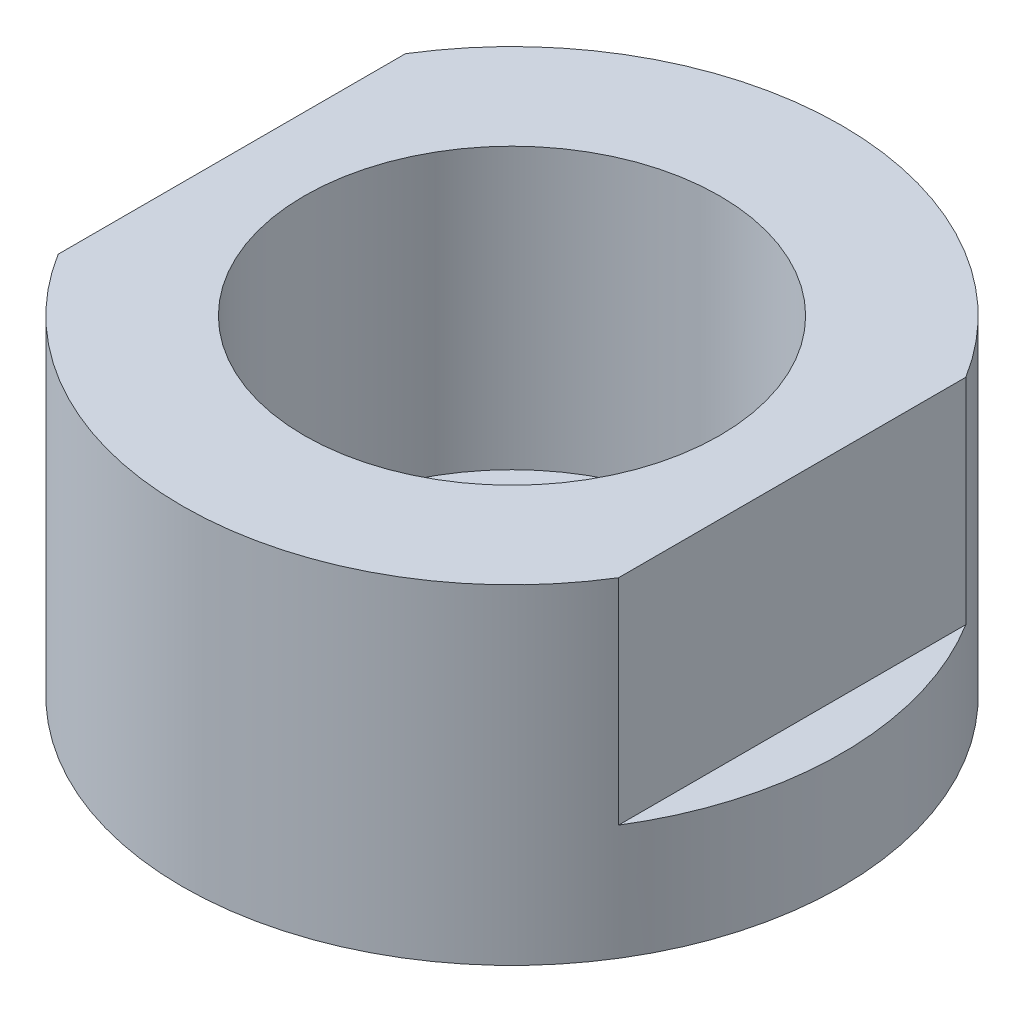
SolidWorks part; units mm, degrees
ref_plane "Front Plane" through (0, 0, 0) normal (0, 0, 1) x (1, 0, 0)
ref_plane "Top Plane" through (0, 0, 0) normal (0, 1, 0) x (1, 0, 0)
ref_plane "Right Plane" through (0, 0, 0) normal (1, 0, 0) x (0, 0, -1)
sketch "Sketch1" plane through (0, 0, 0) normal (0, 1, 0) x (1, 0, 0)
  circle A0 centre (0, 0) radius 25.4
  dimension "D1" = 50.8
extrude "Boss-Extrude1" add sketch "Sketch1" along normal blind 25.4
sketch "Sketch2" plane through (0, 25.4, 0) normal (0, 1, 0) x (1, 0, 0)
  circle A0 centre (0, 0) radius 16
  dimension "D1" = 32
extrude "Cut-Extrude1" cut sketch "Sketch2" against normal offset from surface (21.59 mm away) 3.81 up to face at (0, 0, 25.4)
sketch "Sketch3" plane through (0, 0, 0) normal (0, 0, 1) x (1, 0, 0)
  line L1 (25.4, 25.4) -> (21.59, 25.4)
  line L2 (25.4, 25.4) -> (25.4, 8.89)
  line L3 (25.4, 8.89) -> (21.59, 8.89)
  line L4 (21.59, 25.4) -> (21.59, 8.89)
  line L5 (25.4, 25.4) -> (21.59, 8.89) construction
  line L6 (25.4, 8.89) -> (21.59, 25.4) construction
  line L7 (-25.4, 25.4) -> (-21.59, 25.4)
  line L8 (-25.4, 25.4) -> (-25.4, 8.89)
  line L9 (-25.4, 8.89) -> (-21.59, 8.89)
  line L10 (-21.59, 25.4) -> (-21.59, 8.89)
  line L11 (-25.4, 25.4) -> (-21.59, 8.89) construction
  line L12 (-25.4, 8.89) -> (-21.59, 25.4) construction
  point P4 (23.495, 17.145)
  point P10 (-23.495, 17.145)
  dimension "D1" = 16.51
  dimension "D2" = 3.81
extrude "Cut-Extrude2" cut sketch "Sketch3" against normal up to next and the other way up to next
sketch "Sketch4" plane through (0, 3.81, 0) normal (0, 1, 0) x (1, 0, 0)
  line L0 (0, 0) -> (0, 12.7) construction
  circle A0 centre (0, 12.7) radius 1
  circle A1 centre (10.9985, -6.35) radius 1
  circle A2 centre (-10.9985, -6.35) radius 1
  point P11 (0, 0)
  dimension "D1" = 2
  dimension "D2" = 12.7
  dimension "D3" = 3
extrude "Cut-Extrude3" cut sketch "Sketch4" against normal up to next
